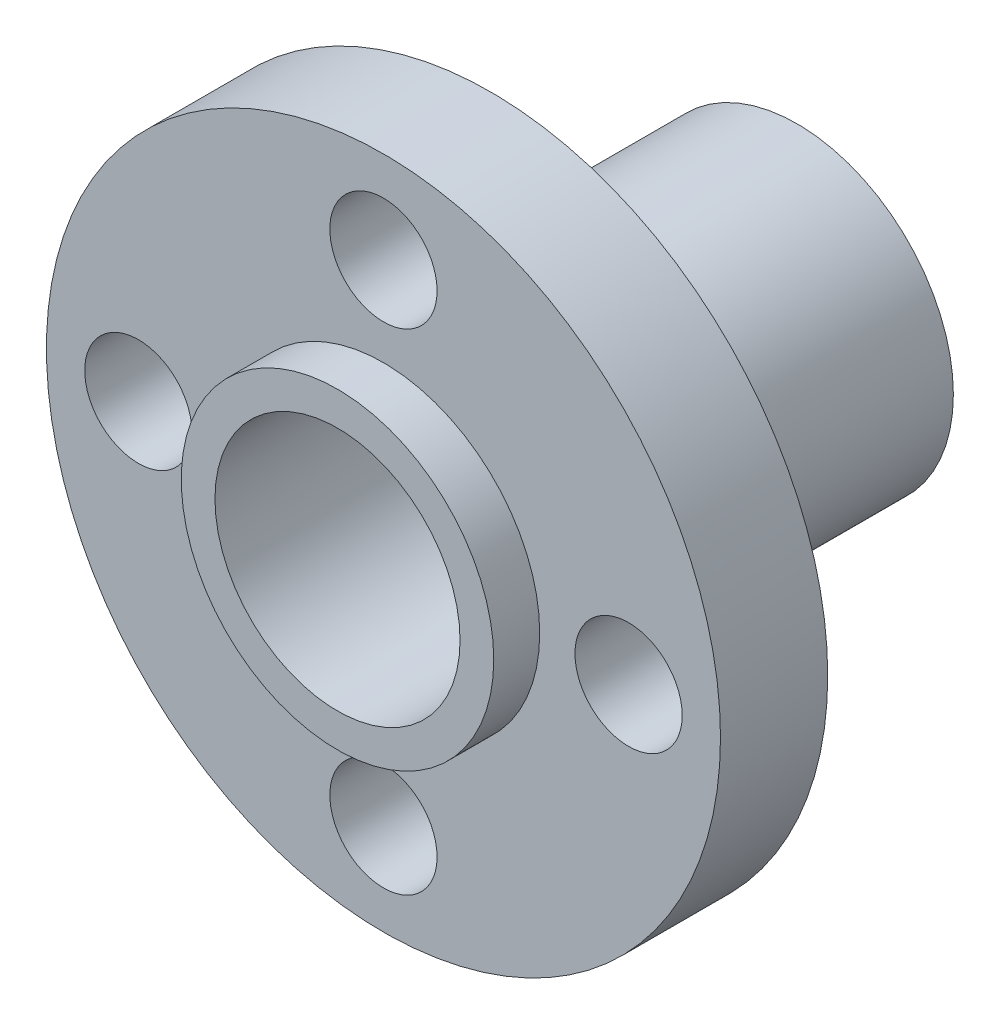
SolidWorks part; units mm, degrees
ref_plane "Plano frontal" through (0, 0, 0) normal (0, 0, 1) x (1, 0, 0)
ref_plane "Plano superior" through (0, 0, 0) normal (0, 1, 0) x (1, 0, 0)
ref_plane "Plano direito" through (0, 0, 0) normal (1, 0, 0) x (0, 0, -1)
sketch "Esboço1" plane through (0, 0, 0) normal (0, 0, 1) x (1, 0, 0)
  circle A0 centre (0, 0) radius 8 construction
  circle A1 centre (0, 0) radius 11
  circle A2 centre (0, 0) radius 5.1
  circle A3 centre (0, 0) radius 4
  circle A4 centre (-8, 0) radius 1.75
  circle A5 centre (0, 8) radius 1.75
  circle A6 centre (8, 0) radius 1.75
  circle A7 centre (0, -8) radius 1.75
  point P17 (0, 0)
  dimension "D1" = 10.2
  dimension "D2" = 22
  dimension "D3" = 16
  dimension "D4" = 8
  dimension "D5" = 3.5
  dimension "D6" = 4
extrude "Ressalto-extrusão1" add sketch "Esboço1" along normal blind 3.5 contours A1 A2 | A2 region at (-10.6889, 0, 0) region at (-4.9558, 0, 0)
extrude "Ressalto-extrusão2" add sketch "Esboço1<3>" along normal blind 1.5 from surface contours A2 region at (-4.9558, 0, 0) starting at face at (1.75, -8, 3.5)
sketch "Esboço1<3>" plane through (0, 0, 0) normal (0, 0, 1) x (1, 0, 0) same geometry as "Esboço1"
extrude "Ressalto-extrusão3" add sketch "Esboço1<5>" against normal blind 10 contours A2 region at (-4.9558, 0, 0)
sketch "Esboço1<5>" plane through (0, 0, 0) normal (0, 0, 1) x (1, 0, 0) same geometry as "Esboço1"
